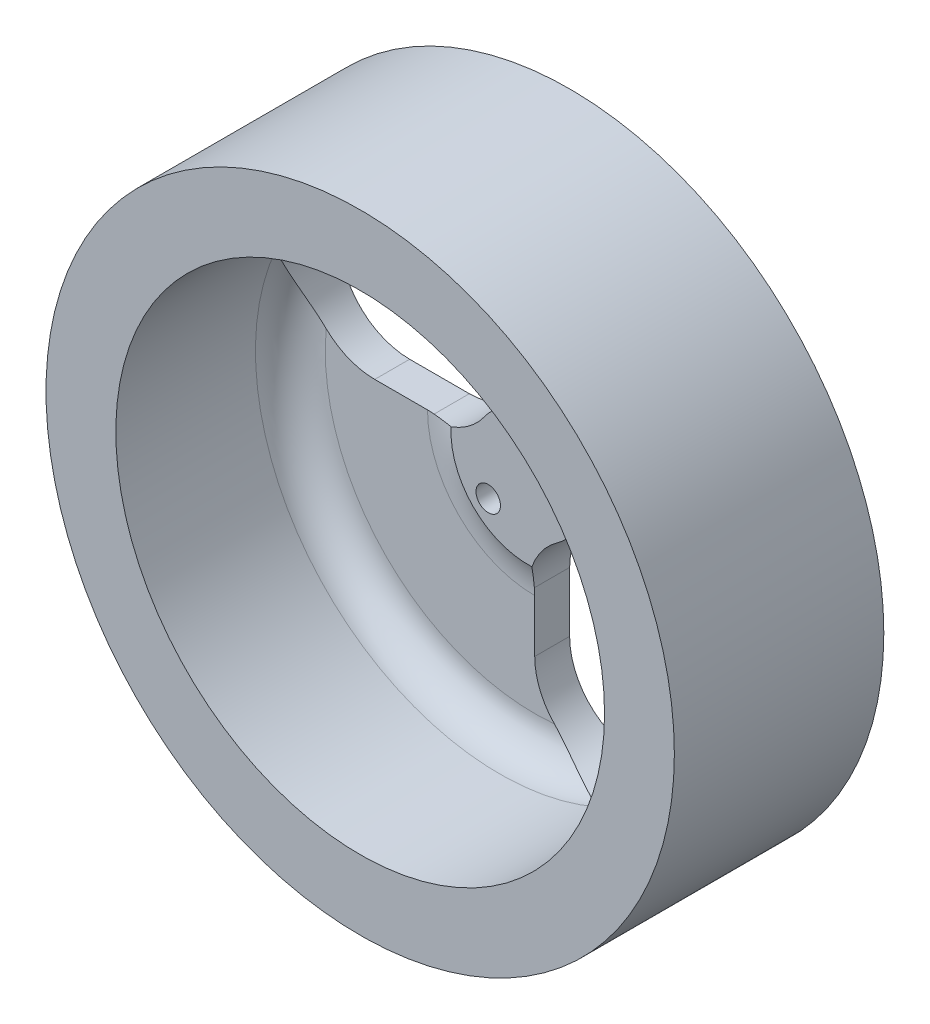
SolidWorks part; units mm, degrees
ref_plane "Front Plane" through (0, 0, 0) normal (0, 0, 1) x (1, 0, 0)
ref_plane "Top Plane" through (0, 0, 0) normal (0, 1, 0) x (1, 0, 0)
ref_plane "Right Plane" through (0, 0, 0) normal (1, 0, 0) x (0, 0, -1)
sketch "Sketch1" plane through (0, 0, 0) normal (0, 0, 1) x (1, 0, 0)
  line L0 (0, 0) -> (0, 4.25) construction
  line L1 (-0.5985, 4.2076) -> (-0.5281, 3.7126)
  line L2 (0.6976, 4.1924) -> (0.6155, 3.6991)
  line L3 (2.4475, 3.4745) -> (2.1596, 3.0657)
  line L4 (1.2864, 4.0506) -> (1.1351, 3.5741)
  line L5 (3.7127, 2.0685) -> (3.2759, 1.8251)
  line L6 (2.9165, 3.0914) -> (2.5734, 2.7277)
  line L7 (4.2425, 0.2528) -> (3.7434, 0.223)
  line L8 (3.969, 1.5198) -> (3.502, 1.341)
  line L9 (3.932, -1.613) -> (3.4694, -1.4233)
  line L10 (4.2353, -0.3528) -> (3.7371, -0.3113)
  line L11 (2.8428, -3.1593) -> (2.5083, -2.7876)
  line L12 (3.6628, -2.1555) -> (3.2319, -1.9019)
  line L13 (1.1905, -4.0799) -> (1.0504, -3.5999)
  line L14 (2.3649, -3.5313) -> (2.0866, -3.1158)
  line L15 (-0.6976, -4.1924) -> (-0.6155, -3.6991)
  line L16 (0.5985, -4.2076) -> (0.5281, -3.7126)
  line L17 (-2.4475, -3.4745) -> (-2.1596, -3.0657)
  line L18 (-1.2864, -4.0506) -> (-1.1351, -3.5741)
  line L19 (-3.7127, -2.0685) -> (-3.2759, -1.8251)
  line L20 (-2.9165, -3.0914) -> (-2.5734, -2.7277)
  line L21 (-4.2425, -0.2528) -> (-3.7434, -0.223)
  line L22 (-3.969, -1.5198) -> (-3.502, -1.341)
  line L23 (-3.932, 1.613) -> (-3.4694, 1.4233)
  line L24 (-4.2353, 0.3528) -> (-3.7371, 0.3113)
  line L25 (-2.8428, 3.1593) -> (-2.5083, 2.7876)
  line L26 (-3.6628, 2.1555) -> (-3.2319, 1.9019)
  line L27 (-1.1905, 4.0799) -> (-1.0504, 3.5999)
  line L28 (-2.3649, 3.5313) -> (-2.0866, 3.1158)
  line L29 (0, 35) -> (0, 7.5)
  line L30 (-7.5, 0) -> (-35, 0)
  line L31 (0, -35) -> (0, -7.5)
  line L32 (35, 0) -> (7.5, 0)
  circle A0 centre (0, 0) radius 4.25
  circle A1 centre (0, 0) radius 3.75
  circle A2 centre (0, 0) radius 7.5
  circle A3 centre (0, 0) radius 1.3
  arc A4 (-0.5985, 4.2076) -> (0.6976, 4.1924) centre (0, 0) cw
  arc A5 (1.2864, 4.0506) -> (2.4475, 3.4745) centre (0, 0) cw
  arc A6 (2.9165, 3.0914) -> (3.7127, 2.0685) centre (0, 0) cw
  arc A7 (3.969, 1.5198) -> (4.2425, 0.2528) centre (0, 0) cw
  arc A8 (4.2353, -0.3528) -> (3.932, -1.613) centre (0, 0) cw
  arc A9 (3.6628, -2.1555) -> (2.8428, -3.1593) centre (0, 0) cw
  arc A10 (2.3649, -3.5313) -> (1.1905, -4.0799) centre (0, 0) cw
  arc A11 (0.5985, -4.2076) -> (-0.6976, -4.1924) centre (0, 0) cw
  arc A12 (-1.2864, -4.0506) -> (-2.4475, -3.4745) centre (0, 0) cw
  arc A13 (-2.9165, -3.0914) -> (-3.7127, -2.0685) centre (0, 0) cw
  arc A14 (-3.969, -1.5198) -> (-4.2425, -0.2528) centre (0, 0) cw
  arc A15 (-4.2353, 0.3528) -> (-3.932, 1.613) centre (0, 0) cw
  arc A16 (-3.6628, 2.1555) -> (-2.8428, 3.1593) centre (0, 0) cw
  arc A17 (-2.3649, 3.5313) -> (-1.1905, 4.0799) centre (0, 0) cw
  circle A18 centre (0, 0) radius 40
  circle A19 centre (0, 0) radius 35
  point P108 (0, 0)
  dimension "D1" = 7.5
  dimension "D2" = 8.5
  dimension "D5" = 2.6
  dimension "D6" = 0.5
  dimension "D9" = 15
  dimension "D10" = 80
  dimension "D11" = 70
  dimension "D3" = 0.6
  dimension "D4" = 0.7
  dimension "D7" = 0.5
  dimension "D8" = 14
extrude "Boss-Extrude1" add sketch "Sketch1" along normal blind 6 contours A1 L26 A0 L23 | A1 L24 A0 L21 | A1 L22 A0 L19 | A1 L20 A0 L17 | A1 L18 A0 L15 | A1 L16 A0 L13 | A1 L14 A0 L11 | A1 L12 A0 L9 | A1 L10 A0 L7 | A1 L8 A0 L5 | A1 L6 A0 L3 | A1 L4 A0 L2 | A1 L1 A0 L27 | A1 L28 A0 L25 | A2 A0 region at (-0.8444, 3.9117, 0) region at (0.9365, 3.8907, 0) region at (-2.458, 3.158, 0) region at (2.5318, 3.0991, 0) region at (-3.5848, 1.7787, 0) region at (3.6257, 1.6937, 0) region at (-4.0015, 0.0472, 0) region at (4.0015, -0.0472, 0) region at (-3.6257, -1.6937, 0) region at (3.5848, -1.7787, 0) region at (-2.5318, -3.0991, 0) region at (2.458, -3.158, 0) region at (-0.9365, -3.8907, 0) region at (0.8444, -3.9117, 0) region at (5.1533, 5.1533, 0)
extrude "Boss-Extrude2" add sketch "Sketch1<5>" along normal blind 5 contours L32 A19 L29 A2 | L30 A19 L31 A2 region at (15.4162, 15.4162, 0) region at (-15.4162, -15.4162, 0)
sketch "Sketch1<5>" plane through (0, 0, 0) normal (0, 0, 1) x (1, 0, 0) same geometry as "Sketch1"
extrude "Boss-Extrude3" add sketch "Sketch1<6>" along normal blind 30 contours A18 A19 region at (-38.8686, 0, 0)
sketch "Sketch1<6>" plane through (0, 0, 0) normal (0, 0, 1) x (1, 0, 0) same geometry as "Sketch1"
fillet "Fillet1" radius 5 2 edges at (-24.7487, -24.7487, 5) (24.7487, 24.7487, 5)
fillet "Fillet2" radius 10 8 edges at (0, -7.5, 2.5) (7.5, 0, 2.5) (0, 7.5, 2.5) (-7.5, 0, 2.5) (0, 35, 5) (35, 0, 5) (0, -35, 5) (-35, 0, 5)
sketch "Sketch2" plane through (0, 0, 6) normal (0, 0, 1) x (1, 0, 0)
  circle A0 centre (0, 0) radius 4.75
  dimension "D1" = 9.5
extrude "Boss-Extrude4" add sketch "Sketch2" against normal up to surface (6 mm away) up to face at (-11.92, 11.92, 0)
sketch "Sketch3" plane through (0, 0, 0) normal (0, 0, -1) x (-1, 0, 0)
  arc A0 (-0.5875, -10.9843) -> (10.9843, 0.5875) centre (0, 0) ccw
  arc A1 (0, 14.3614) -> (4.2857, 6.1549) centre (10, 14.3614) ccw construction
  arc A2 (-6.1549, -4.2857) -> (-4.2857, -6.1549) centre (0, 0) ccw construction
  arc A3 (6.1549, 4.2857) -> (4.2857, 6.1549) centre (0, 0) ccw construction
  arc A4 (6.1549, 4.2857) -> (14.3614, 0) centre (14.3614, 10) ccw construction
  arc A5 (-6.1549, -4.2857) -> (-14.3614, 0) centre (-14.3614, -10) ccw construction
  arc A6 (0, -14.3614) -> (-4.2857, -6.1549) centre (-10, -14.3614) ccw construction
  arc A7 (-0.5875, -10.9843) -> (-4.2857, -6.1549) centre (-10, -14.3614) ccw
  arc A8 (-6.1549, -4.2857) -> (-4.2857, -6.1549) centre (0, 0) ccw
  arc A9 (-6.1549, -4.2857) -> (-10.9843, -0.5875) centre (-14.3614, -10) ccw
  arc A10 (6.1549, 4.2857) -> (10.9843, 0.5875) centre (14.3614, 10) ccw
  arc A11 (6.1549, 4.2857) -> (4.2857, 6.1549) centre (0, 0) ccw
  arc A12 (0.5875, 10.9843) -> (4.2857, 6.1549) centre (10, 14.3614) ccw
  arc A13 (0.5875, 10.9843) -> (-10.9843, -0.5875) centre (0, 0) ccw
  point P9 (-5.3033, -5.3033)
  dimension "D1" = 22
extrude "Boss-Extrude5" add sketch "Sketch3" against normal up to surface (6 mm away) up to face at (7.5, 0, 6)
fillet "Fillet3" radius 10 2 edges at (7.7782, 7.7782, 5) (-7.7782, -7.7782, 5)
sketch "Sketch4" plane through (0, 0, 6) normal (0, 0, 1) x (1, 0, 0)
  line L0 (7.7782, 7.7782) -> (-7.7782, -7.7782) construction
  arc A0 (10.9843, -0.5875) -> (-0.5875, 10.9843) centre (0, 0) ccw construction
  arc A1 (-10.9843, 0.5875) -> (0.5875, -10.9843) centre (0, 0) ccw construction
  circle A2 centre (-5.6569, -5.6569) radius 1.75
  circle A3 centre (5.6569, 5.6569) radius 1.75
  dimension "D1" = 3.5
  dimension "D2" = 3.5
  dimension "D3" = 8
  dimension "D4" = 8
extrude "Cut-Extrude1" cut sketch "Sketch4" against normal through all
sketch "Sketch7" plane through (0, 0, 30) normal (0, 0, 1) x (1, 0, 0)
  circle A0 centre (0, 0) radius 40 construction
  circle A1 centre (0, 0) radius 40
  circle A2 centre (0, 0) radius 45
  dimension "D1" = 90
extrude "Boss-Extrude6" add sketch "Sketch7" against normal up to surface (30 mm away) up to face at (-3.9069, -5.6569, 0)
